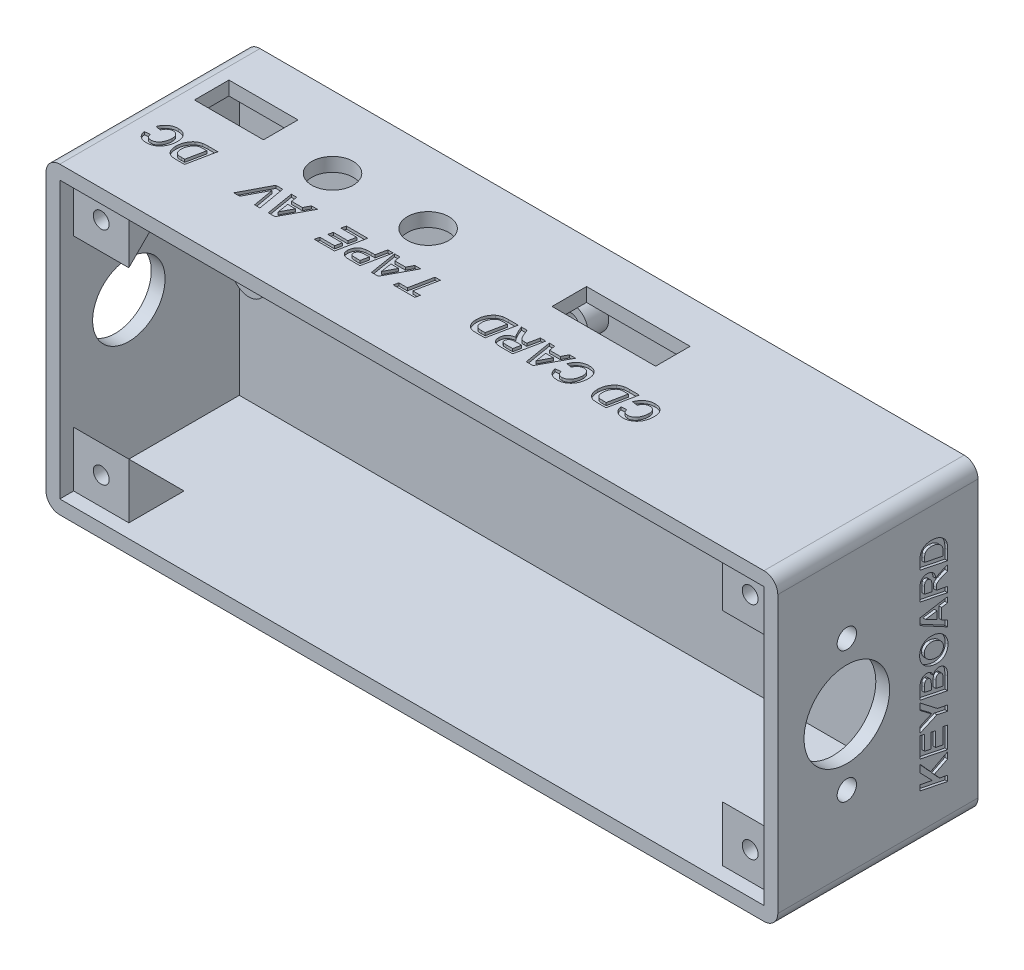
SolidWorks part; units mm, degrees
material "ABS"
ref_plane "Спереди" through (0, 0, 0) normal (0, 0, 1) x (1, 0, 0)
ref_plane "Сверху" through (0, 0, 0) normal (0, 1, 0) x (1, 0, 0)
ref_plane "Справа" through (0, 0, 0) normal (1, 0, 0) x (0, 0, -1)
sketch "Эскиз1" plane through (0, 0, 0) normal (0, 0, 1) x (1, 0, 0)
  line L1 (-53, -22) -> (53, -22)
  line L2 (-53, -22) -> (-53, 22)
  line L3 (-53, 22) -> (53, 22)
  line L4 (53, -22) -> (53, 22)
  line L5 (-53, -22) -> (53, 22) construction
  line L6 (-53, 22) -> (53, -22) construction
  point P0 (0, 0)
  dimension "D1" = 106
  dimension "D2" = 44
extrude "CaseBody" add sketch "Эскиз1" along normal blind 3
sketch "Эскиз2" plane through (0, 0, 3) normal (0, 0, 1) x (1, 0, 0)
  line L0 (53, 22) -> (-53, 22) construction
  line L1 (-51, -20) -> (51, -20)
  line L2 (-51, -20) -> (-51, 20)
  line L3 (-51, 20) -> (51, 20)
  line L4 (51, -20) -> (51, 20)
  line L5 (-51, -20) -> (51, 20) construction
  line L6 (-51, 20) -> (51, -20) construction
  line L7 (53, -22) -> (53, 22) construction
  line L9 (-53, -22) -> (53, -22)
  line L10 (-53, -22) -> (-53, 22)
  line L11 (-53, 22) -> (53, 22)
  line L12 (53, -22) -> (53, 22)
  line L13 (-53, -22) -> (53, 22) construction
  line L14 (-53, 22) -> (53, -22) construction
  point P0 (0, 0)
  point P10 (0, 0)
  dimension "D1" = 2
  dimension "D2" = 2
extrude "CaseBody2" add sketch "Эскиз2" along normal blind 26
sketch "Эскиз3" plane through (0, 0, 3) normal (0, 0, 1) x (1, 0, 0)
  line L0 (51, 20) -> (-51, 20) construction
  line L1 (-46.625, -1.47) -> (46.625, -1.47) construction
  line L2 (-46.625, -1.47) -> (-46.625, 16.18) construction
  line L3 (-46.625, 16.18) -> (46.625, 16.18) construction
  line L4 (46.625, -1.47) -> (46.625, 16.18) construction
  line L5 (-46.625, -1.47) -> (46.625, 16.18) construction
  line L6 (-46.625, 16.18) -> (46.625, -1.47) construction
  circle A0 centre (-46.625, -1.47) radius 2.5
  circle A1 centre (46.625, -1.47) radius 2.5
  circle A2 centre (0.005, 16.18) radius 2.5
  point P0 (0, 0)
  point P13 (0, 7.355)
  dimension "D4" = 5
  dimension "D1" = 93.25
  dimension "D2" = 17.65
  dimension "D3" = 46.63
  dimension "D5" = 3.82
extrude "SizifXXSFix" add sketch "Эскиз3" along normal blind 3
sketch "Эскиз4" plane through (0, 0, 6) normal (0, 0, 1) x (1, 0, 0)
  circle A0 centre (-46.625, -1.47) radius 1.2
  circle A1 centre (0.005, 16.18) radius 1.2
  circle A2 centre (46.625, -1.47) radius 1.2
  dimension "D1" = 2.4
extrude "Holes2_5" cut sketch "Эскиз4" against normal blind 5.6
sketch "Эскиз5" plane through (0, 22, 0) normal (0, 1, 0) x (1, 0, 0)
  line L1 (-49.3, -6.2) -> (-39.3, -6.2)
  line L2 (-49.3, -6.2) -> (-49.3, -11.2)
  line L3 (-49.3, -11.2) -> (-39.3, -11.2)
  line L4 (-39.3, -6.2) -> (-39.3, -11.2)
  line L5 (-49.3, -6.2) -> (-39.3, -11.2) construction
  line L6 (-49.3, -11.2) -> (-39.3, -6.2) construction
  line L7 (2.5, -6.2) -> (17.5, -6.2)
  line L8 (2.5, -6.2) -> (2.5, -11.2)
  line L9 (2.5, -11.2) -> (17.5, -11.2)
  line L10 (17.5, -6.2) -> (17.5, -11.2)
  line L11 (2.5, -6.2) -> (17.5, -11.2) construction
  line L12 (2.5, -11.2) -> (17.5, -6.2) construction
  line L13 (53, 0) -> (-53, 0) construction
  line L14 (-53, -29) -> (-53, 0) construction
  circle A0 centre (-30.1, -10.4) radius 3
  circle A1 centre (-16.25, -10.4) radius 3
  point P0 (-44.3, -8.7)
  point P9 (10, -8.7)
  dimension "D5" = 6
  dimension "D2" = 10
  dimension "D3" = 6.2
  dimension "D4" = 5
  dimension "D6" = 13.85
  dimension "D7" = 14.2
  dimension "D8" = 26.25
  dimension "D9" = 10.4
  dimension "D10" = 5
  dimension "D11" = 15
  dimension "D12" = 22.9
extrude "SizifXXS_Holes" cut sketch "Эскиз5" against normal up to next
sketch "Эскиз7" plane through (53, 0, 0) normal (1, 0, 0) x (0, 0, -1)
  line L0 (-20, 0) -> (-6.0564, 0) construction
  line L1 (-29, -22) -> (-29, 22) construction
  circle A0 centre (-19, 0) radius 6.2
  circle A1 centre (-19, -9.5) radius 1.4
  circle A2 centre (-19, 9.5) radius 1.4
  dimension "D1" = 12.4
  dimension "D4" = 2.8
  dimension "D2" = 10
  dimension "D3" = 19
extrude "PS2Hole" cut sketch "Эскиз7" against normal up to next
sketch "Эскиз8" plane through (51, 0, 0) normal (-1, 0, 0) x (0, 0, 1)
  line L0 (27, 20) -> (27, 12)
  line L1 (29, 20) -> (3, 20) construction
  line L2 (27, 12) -> (19, 20)
  line L3 (19, 20) -> (27, 20)
  line L4 (29, -20) -> (29, 20) construction
  dimension "D1" = 8
  dimension "D2" = 8
  dimension "D3" = 2
extrude "CaseTopFix" add sketch "Эскиз8" along normal blind 8
sketch "Эскиз9" plane through (0, 0, 27) normal (0, 0, 1) x (1, 0, 0)
  line L0 (43, 12) -> (43, 20) construction
  line L1 (43, 20) -> (51, 20) construction
  line L2 (43, 20) -> (43, 12) construction
  line L3 (43, 12) -> (51, 12) construction
  line L4 (51, 20) -> (51, 12) construction
  line L5 (43, 20) -> (51, 12) construction
  line L6 (43, 12) -> (51, 20) construction
  line L7 (43, 20) -> (51, 20) construction
  circle A0 centre (47, 16) radius 1.15
  point P0 (47, 16)
  dimension "D1" = 2.3
extrude "CaseTopHoles" cut sketch "Эскиз9" against normal up to next
mirror "CaseTopHoles1" about plane through (0, 0, 0) normal (0, 1, 0) of "CaseTopHoles", "CaseTopFix"
mirror "CaseTopHoles2" about plane through (0, 0, 0) normal (1, 0, 0) of "CaseTopHoles", "CaseTopHoles1", "CaseTopFix"
fillet "Fillet" radius 2 4 edges at (-53, 22, 14.5) (53, 22, 14.5) (53, -22, 14.5) (-53, -22, 14.5)
sketch "Эскиз10" plane through (0, 22, 0) normal (0, 1, 0) x (1, 0, 0)
  line L0 (51, 0) -> (-51, 0) construction
  line L1 (-53, -29) -> (-53, 0) construction
  text T0 "<r180>VA</r>" font "Times New Roman" height 4
  text T1 "<r180>EPAT</r>" font "Times New Roman" height 4
  text T2 "<r180>CD</r>" font "Times New Roman" height 4
  text T3 "<r180>DRAC DC</r>" font "Times New Roman" height 4
  dimension "D1" = 16
  dimension "D2" = 22.5962
  dimension "D3" = 11.2585
  dimension "D4" = 14.4528
  dimension "D5" = 21.8
extrude "InterfaceInfo" cut sketch "Эскиз10" against normal blind 0.4
sketch "Эскиз11" plane through (53, 0, 0) normal (1, 0, 0) x (0, 0, -1)
  line L0 (-4.4, -16) -> (-4.4, 15) construction
  line L1 (0, -20) -> (0, 20) construction
  line L2 (0, -22) -> (-29, -22) construction
  text T0 "KEYBOARD" font "Arial" height 4
  dimension "D1" = 4.4
  dimension "D2" = 31
  dimension "D3" = 6
extrude "PS2Info" cut sketch "Эскиз11" against normal blind 0.4
sketch "Эскиз12" plane through (0, 20, 0) normal (0, -1, 0) x (1, 0, 0)
  line L1 (-53, 0) -> (-53, 29) construction
  line L2 (-51, 0) -> (51, 0) construction
  text T0 "© Peter Ukhov 2023" font "Arial" height 6
  dimension "D1" = 16
  dimension "D2" = 14
sketch "Эскиз13" plane through (-53, 0, 0) normal (-1, 0, 0) x (0, 0, 1)
  line L0 (29, 20) -> (29, -20) construction
  circle A0 centre (19, 0) radius 5.25
  dimension "D1" = 10.5
  dimension "D2" = 10
extrude "ButtonHole" cut sketch "Эскиз13" against normal up to next
sketch "Эскиз14" plane through (-53, 0, 0) normal (-1, 0, 0) x (0, 0, 1)
  line L0 (6.2274, 10.1387) -> (6.2274, -12.1287) construction
  text T0 "POWER" font "Arial" height 4
extrude "ButtonInfo" cut sketch "Эскиз14" against normal blind 0.4
extrude "CopyLeft" cut sketch "Эскиз12" against normal blind 0.4
equation "\"D1@Эскиз1\"=100+2*2+2"
equation "\"D2@Эскиз1\"=40+2*2"
equation "\"D5@Эскиз3\"=3.42+0.4"
equation "\"D2@Эскиз7\"=14/2+3"
